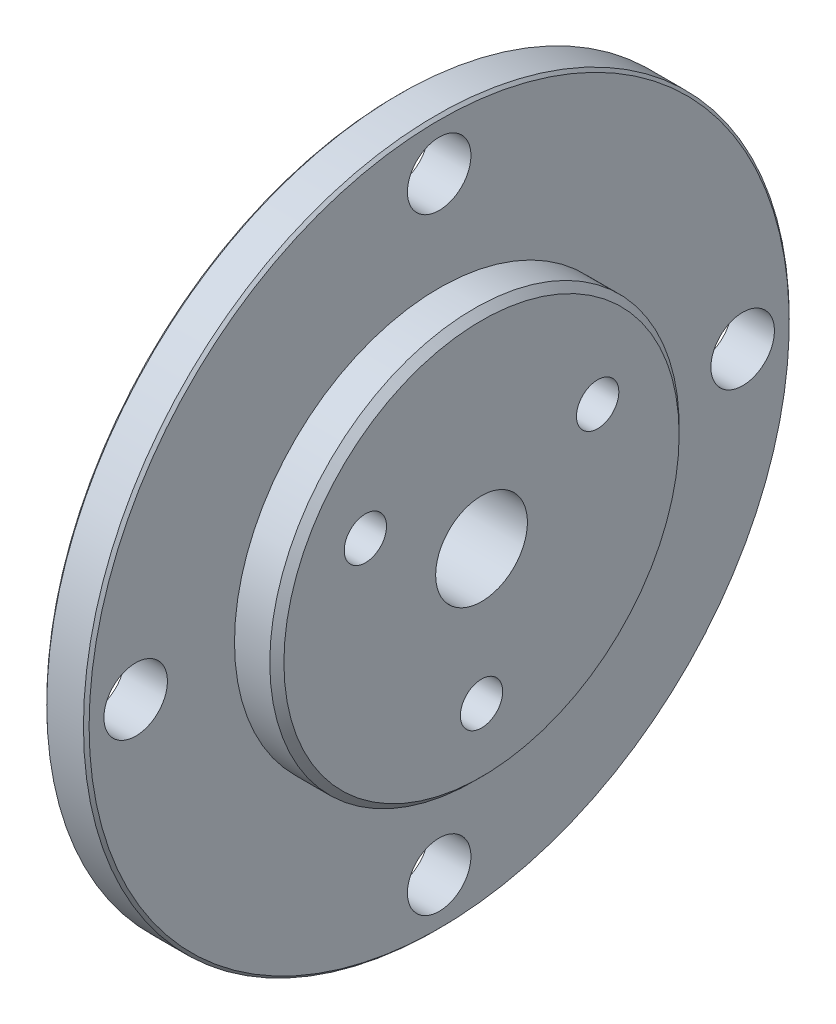
SolidWorks part; units mm, degrees
ref_plane "Face" through (0, 0, 0) normal (0, 0, 1) x (1, 0, 0)
ref_plane "Dessus" through (0, 0, 0) normal (0, 1, 0) x (1, 0, 0)
ref_plane "Droite" through (0, 0, 0) normal (1, 0, 0) x (0, 0, -1)
sketch "Esquisse1" plane through (0, 0, 0) normal (0, 0, 1) x (1, 0, 0)
  line L0 (-30.7302, 0) -> (30.7302, 0) construction
  line L1 (-3, 3.25) -> (-3, 25)
  line L2 (-3, 25) -> (0, 25)
  line L3 (0, 25) -> (0, 14.5)
  line L4 (0, 14.5) -> (3, 14.5)
  line L5 (3, 14.5) -> (3, 3.25)
  line L6 (3, 3.25) -> (-3, 3.25)
  dimension "D1" = 25
  dimension "D2" = 6.5
  dimension "D3" = 14.5
  dimension "D4" = 3
  dimension "D5" = 6
revolve "Base-Révolution" add sketch "Esquisse1" angle 360 about L0
chamfer "Chanfrein1" distance 0.5 angle 45 1 edges at (3, 0, 14.5)
chamfer "Chanfrein2" distance 0.2 angle 45 2 edges at (-3, 0, 25) (0, 0, 25)
sketch "Esquisse2" plane through (3, 0, 0) normal (1, 0, 0) x (0, 0, -1)
  line L0 (0, 0) -> (0, 16.5913) construction
  line L1 (0, 0) -> (-14.354, 8.2873) construction
  circle A0 centre (-8.2272, 4.75) radius 1.5
  dimension "D3" = 3
  dimension "D1" = 60
  dimension "D2" = 9.5
extrude "Trou de fixation du moteur" cut sketch "Esquisse2" against normal through all
ref_axis "Axe1" through (19.2698, 0, 0) along (-1, 0, 0)
pattern_circular "Répétition des 3 trous" count 3 over 360 about axis through (19.2698, 0, 0) along (-1, 0, 0) of "Trou de fixation du moteur"
sketch "Esquisse3" plane through (-3, 0, 0) normal (-1, 0, 0) x (0, 0, 1)
  line L0 (0, 0) -> (0, 21.1514) construction
  circle A0 centre (0, 21.5) radius 2.25
  dimension "D2" = 4.5
  dimension "D1" = 21.5
extrude "Trou de fixation de la bride" cut sketch "Esquisse3" against normal through all
pattern_circular "Répétition des 4 trous" count 4 over 360 about axis through (19.2698, 0, 0) along (-1, 0, 0) of "Trou de fixation de la bride"
